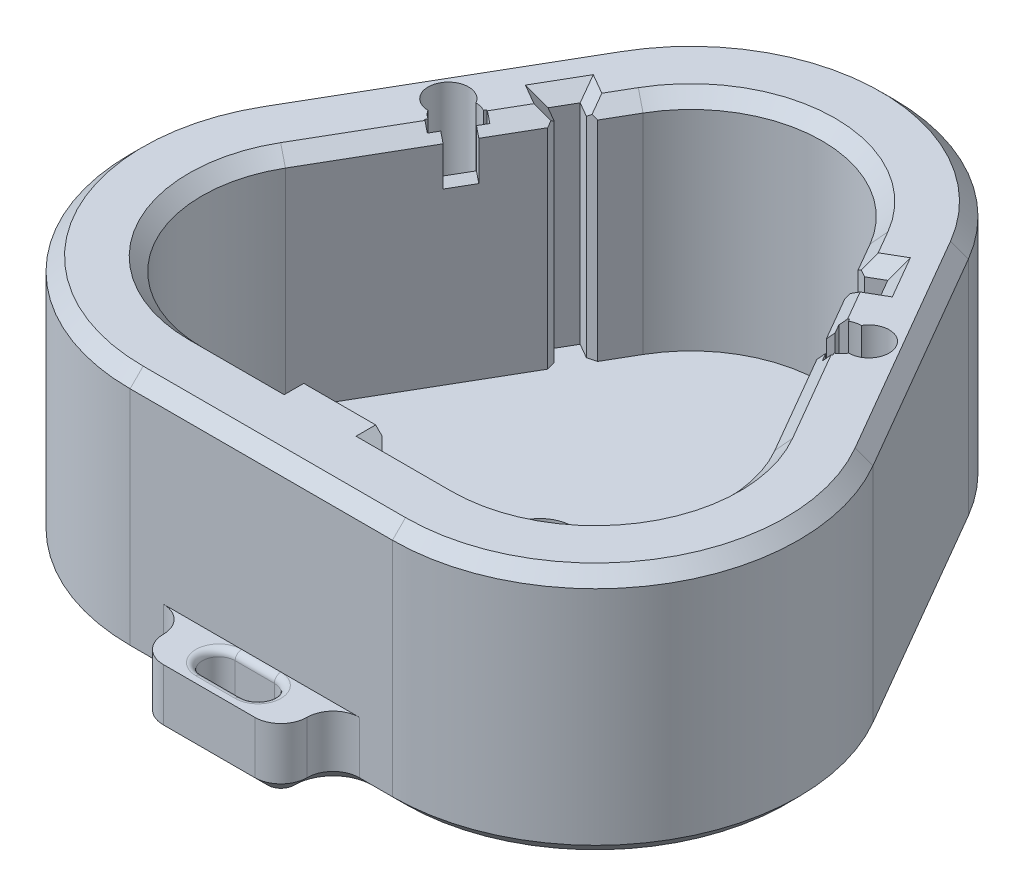
SolidWorks part; units mm, degrees
ref_plane "Front Plane" through (0, 0, 0) normal (0, 0, 1) x (1, 0, 0)
ref_plane "Top Plane" through (0, 0, 0) normal (0, 1, 0) x (1, 0, 0)
ref_plane "Right Plane" through (0, 0, 0) normal (1, 0, 0) x (0, 0, -1)
sketch "Sketch1" plane through (0, 0, 0) normal (0, 1, 0) x (1, 0, 0)
  line L0 (0, 11.5518) -> (-10.0362, -5.7759) construction
  line L1 (-10.0362, -5.7759) -> (10.0362, -5.7759) construction
  line L2 (10.0362, -5.7759) -> (0, 11.5518) construction
  line L3 (-10.0362, -5.7759) -> (5.0181, 2.8879) construction
  line L4 (-5.0181, 2.8879) -> (10.0362, -5.7759) construction
  line L5 (-8.6846, 16.5819) -> (-18.7208, -0.7458)
  line L6 (-10.0362, -15.8121) -> (10.0362, -15.8121)
  line L7 (8.6846, 16.5819) -> (18.7208, -0.7458)
  line L8 (0, 21.5879) -> (0, -15.8121) construction
  line L9 (-13.4439, 19.3385) -> (-23.4801, 2.0108)
  line L10 (-10.0362, -21.3121) -> (10.0362, -21.3121)
  line L11 (13.4439, 19.3385) -> (23.4801, 2.0108)
  line L25 (-3.75, -15.3121) -> (3.75, -15.3121)
  line L26 (-3.75, -15.8121) -> (-3.75, -15.3121)
  line L27 (3.75, -15.3121) -> (3.75, -15.8121)
  line L28 (0, -15.2648) -> (0, -15.7648) construction
  line L29 (-3.75, -15.8121) -> (3.75, -15.8121)
  line L34 (8.6846, 16.5819) -> (18.7208, -0.7458) construction
  line L35 (-8.6846, 16.5819) -> (-18.7208, -0.7458) construction
  line L36 (-10.2087, 13.9505) -> (-11.7663, 14.8527)
  line L37 (-11.7663, 14.8527) -> (-12.6685, 13.2951)
  line L38 (-12.6685, 13.2951) -> (-11.1109, 12.3929)
  line L39 (-11.1109, 12.3929) -> (-10.2087, 13.9505)
  line L40 (10.2087, 13.9505) -> (11.7663, 14.8527)
  line L41 (11.7663, 14.8527) -> (12.6685, 13.2951)
  line L42 (12.6685, 13.2951) -> (11.1109, 12.3929)
  line L43 (-13.3501, 9.5244) -> (-15.1043, 6.4957)
  line L44 (-15.1043, 6.4957) -> (-15.6235, 6.7965)
  line L45 (-15.6235, 6.7965) -> (-13.8693, 9.8251)
  line L46 (-13.8693, 9.8251) -> (-13.3501, 9.5244)
  line L47 (13.8693, 9.8251) -> (13.3501, 9.5244)
  line L48 (15.1043, 6.4957) -> (15.6235, 6.7965)
  line L49 (15.6235, 6.7965) -> (13.8693, 9.8251)
  line L50 (13.3501, 9.5244) -> (15.1043, 6.4957)
  arc A1 (-18.7208, -0.7458) -> (-10.0362, -15.8121) centre (-10.0362, -5.7759) ccw
  arc A2 (10.0362, -15.8121) -> (18.7208, -0.7458) centre (10.0362, -5.7759) ccw
  arc A5 (8.6846, 16.5819) -> (-8.6846, 16.5819) centre (0, 11.5518) ccw
  arc A6 (13.4439, 19.3385) -> (-13.4439, 19.3385) centre (0, 11.5518) ccw
  arc A7 (-23.4801, 2.0108) -> (-10.0362, -21.3121) centre (-10.0362, -5.7759) ccw
  arc A8 (10.0362, -21.3121) -> (23.4801, 2.0108) centre (10.0362, -5.7759) ccw
  arc A9 (-13.9696, 9.6521) -> (-15.5233, 6.9695) centre (-14.7464, 8.3108) ccw
  arc A10 (13.9696, 9.6521) -> (15.5233, 6.9695) centre (14.7464, 8.3108) cw
  circle A11 centre (-16.0877, 9.0877) radius 1.55
  circle A12 centre (16.0877, 9.0877) radius 1.55
  point P5 (0, 21.5879)
  point P7 (0, 0)
  point P28 (0, -15.3121)
  point P50 (0, 0)
  dimension "D1" = 37.4
  dimension "D2" = 5.5
  dimension "D8" = 3.1
  dimension "D3" = 3.5
  dimension "D4" = 20.0723
  dimension "D5" = 1.8
  dimension "D7" = 3.0409
  dimension "D9" = 0.6
  dimension "D10" = 0.5
  dimension "D11" = 0.5
  dimension "D12" = 5.3545
  dimension "D6" = 7.5
extrude "Boss-Extrude1" add sketch "Sketch1" along normal blind 17 contours L10 A8 L11 A6 L9 A7 A9 L45 L46 L43 L44 A5 L7 L40 L41 L42 A2 L6 A1 L5 L38 L37 L36 L49 A10 L48 L50 L47 | L27 L25 L26 L6 region at (0, 0, 15.5621) region at (0, 0, -26.3838)
chamfer "Chamfer1" distance 0.5 angle 45 4 edges at (10.2087, 8.5, -13.9505) (-10.2087, 8.5, -13.9505) (11.1109, 8.5, -12.3929) (-11.1109, 8.5, -12.3929) tangent propagation no
extrude "Boss-Extrude2" add sketch "Sketch1<4>" against normal blind 2 contours A9 A11 | A11 A9 | A10 A12 | A10 A12 | L11 A8 L10 A7 L9 A6 region at (-15.4171, 0, -8.6992) region at (-16.5183, 0, -9.337) region at (15.4171, 0, -8.6992) region at (16.5183, 0, -9.337)
sketch "Sketch1<4>" plane through (0, 0, 0) normal (0, 1, 0) x (1, 0, 0) same geometry as "Sketch1"
sketch "Sketch2" plane through (0, -2, 0) normal (0, -1, 0) x (1, 0, 0)
  line L0 (5.5, 21.3121) -> (5.5, 25.3121)
  line L5 (5.5, 25.3121) -> (-5.5, 25.3121)
  line L6 (-5.5, 25.3121) -> (-5.5, 21.3121)
  line L7 (-5.5, 21.3121) -> (5.5, 21.3121)
  line L8 (-1.5, 23.0621) -> (1.5, 23.0621) construction
  line L9 (-1.5, 24.3121) -> (1.5, 24.3121)
  line L10 (-1.5, 21.8121) -> (1.5, 21.8121)
  line L11 (-10.0362, 21.3121) -> (10.0362, 21.3121) construction
  arc A6 (-1.5, 24.3121) -> (-1.5, 21.8121) centre (-1.5, 23.0621) ccw
  arc A7 (1.5, 21.8121) -> (1.5, 24.3121) centre (1.5, 23.0621) ccw
  circle A8 centre (0, 0) radius 2.5
  point P2 (0, 21.3121)
  point P18 (0, 25.3121)
  point P21 (0, 23.0621)
  dimension "D4" = 5.5
  dimension "D6" = 5
  dimension "D1" = 11
  dimension "D2" = 4
  dimension "D3" = 2.5
  dimension "D5" = 0.5
extrude "Cut-Extrude2" cut sketch "Sketch2" against normal up to next contours A8 region at (0, -2, 0)
extrude "Boss-Extrude3" add sketch "Sketch2<2>" against normal blind 5 contours L5 L6 L0 A7 L10 A6 L9 region at (0, -2, 21.4291)
sketch "Sketch2<2>" plane through (0, -2, 0) normal (0, -1, 0) x (1, 0, 0) same geometry as "Sketch2"
fillet "Fillet1" radius 2 4 edges at (5.5, 0.5, 21.3121) (5.5, 0.5, 25.3121) (-5.5, 0.5, 25.3121) (-5.5, 0.5, 21.3121)
fillet "Fillet2" radius 0.5 4 edges at (0, 3, 24.3121) (2.75, 3, 23.0621) (0, 3, 21.8121) (-2.75, 3, 23.0621)
chamfer "Chamfer4" distance 1 angle 45 18 edges at (0, -2, 25.3121) (18.462, 17, -10.6747) (0, 17, -27.0879) (23.4963, 17, 13.5346) (-18.462, 17, -10.6747) (0, 17, 21.3121) (-23.4963, 17, 13.5346) (6.0858, -2, 21.8978) (8.7681, -2, 21.3121) (4.9142, -2, 24.7263) (23.4963, -2, 13.5346) (18.462, -2, -10.6747) (-4.9142, -2, 24.7263) (0, -2, -27.0879) (-6.0858, -2, 21.8978) (-18.462, -2, -10.6747) (-8.7681, -2, 21.3121) (-23.4963, -2, 13.5346)
sketch "Sketch3" plane through (0, 17, 0) normal (0, 1, 0) x (1, 0, 0)
  line L0 (-13.726, 8.8754) -> (-13.2934, 8.6248)
  line L2 (-13.2934, 8.6248) -> (-14.2958, 6.8941)
  line L3 (-11.3615, 11.9602) -> (-18.7208, -0.7458) construction
  line L4 (-14.2958, 6.8941) -> (-14.7284, 7.1447)
  line L5 (-14.7284, 7.1447) -> (-13.726, 8.8754)
  line L6 (-13.3501, 9.5244) -> (-15.1043, 6.4957) construction
  line L7 (0, -10.45) -> (0, 10.45) construction
  line L8 (14.7284, 7.1447) -> (13.726, 8.8754)
  line L9 (14.2958, 6.8941) -> (14.7284, 7.1447)
  line L10 (13.2934, 8.6248) -> (14.2958, 6.8941)
  line L11 (13.726, 8.8754) -> (13.2934, 8.6248)
  line L12 (-11.3615, 11.9602) -> (-18.7208, -0.7458) construction
  point P10 (-14.2272, 8.0101)
  dimension "D1" = 2
extrude "Cut-Extrude3" cut sketch "Sketch3" against normal blind 3
chamfer "Chamfer5" distance 1 angle 45 21 edges at (13.7946, 14, -7.7595) (-13.7946, 14, -7.7595) (11.2039, 17, -14.5269) (12.2174, 17, -14.0739) (12.106, 17, -12.9693) (12.3274, 17, -10.2925) (16.5083, 17, -3.0742) (18.7312, 17, 10.7879) (-6.8931, 17, 15.8121) (3.75, 17, 15.5621) (-3.75, 17, 15.5621) (6.8931, 17, 15.8121) (-18.7312, 17, 10.7879) (-16.5083, 17, -3.0742) (-12.3274, 17, -10.2925) (-12.106, 17, -12.9693) (-11.2039, 17, -14.5269) (-12.2174, 17, -14.0739) (9.3214, 17, -15.4825) (-9.3214, 17, -15.4825) (0, 17, -21.5879)
chamfer "Chamfer6" distance 0.5 angle 45 2 edges at (3.75, 8, 15.3121) (-3.75, 8, 15.3121)
